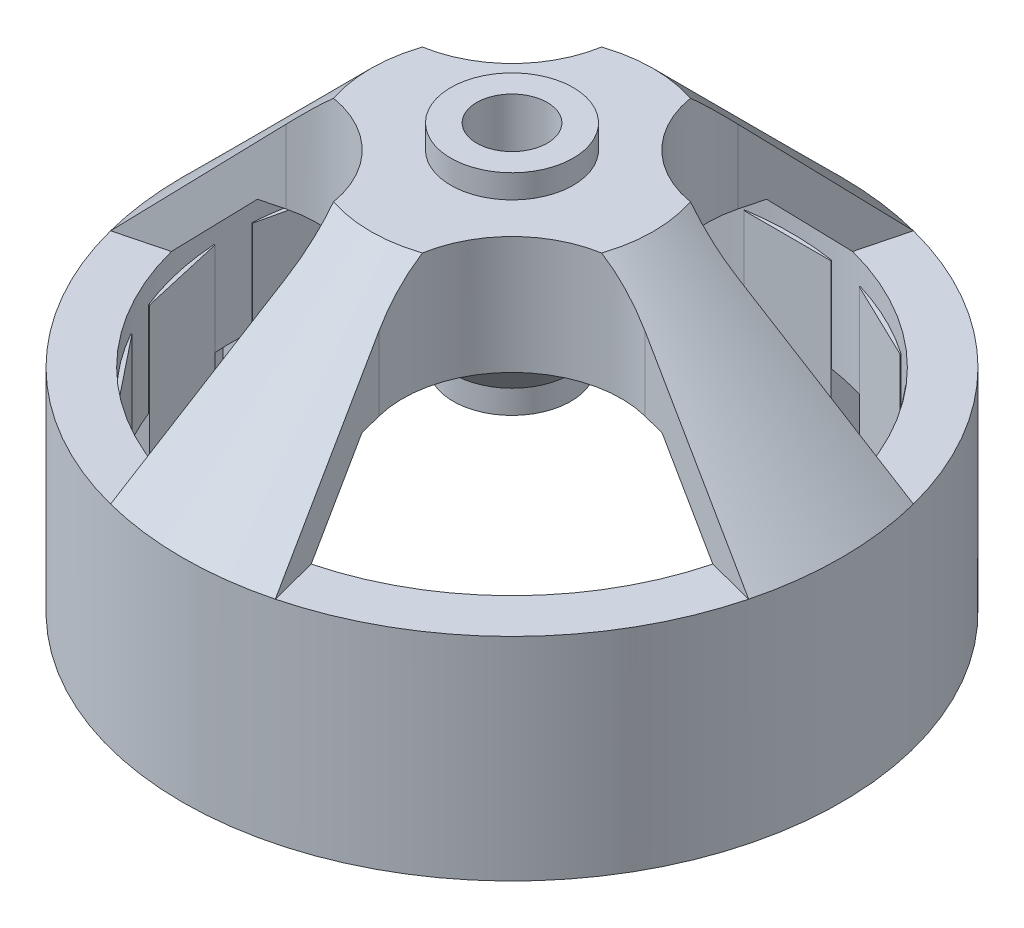
SolidWorks part; units mm, degrees
ref_plane "Front Plane" through (0, 0, 0) normal (0, 0, 1) x (1, 0, 0)
ref_plane "Top Plane" through (0, 0, 0) normal (0, 1, 0) x (1, 0, 0)
ref_plane "Right Plane" through (0, 0, 0) normal (1, 0, 0) x (0, 0, -1)
sketch "Sketch1" plane through (0, 0, 0) normal (0, 0, 1) x (1, 0, 0)
  line L0 (0, 0) -> (0, 18) construction
  line L1 (14, 0) -> (14, 9)
  line L2 (14, 9) -> (6, 17)
  line L3 (6, 17) -> (2.6, 17)
  line L4 (2.6, 17) -> (2.6, 18)
  line L5 (2.6, 18) -> (1.5, 18)
  line L6 (1.5, 18) -> (1.5, 9)
  line L7 (14, 0) -> (13.5, 0)
  line L8 (1.5, 9) -> (2.5, 9)
  line L9 (2.5, 9) -> (2.5, 10)
  line L10 (2.5, 10) -> (4.5, 12)
  line L11 (4.5, 12) -> (8.8787, 12)
  line L12 (8.8787, 12) -> (13.5, 7.3787)
  line L13 (13.5, 7.3787) -> (13.5, 0)
  dimension "D1" = 18
  dimension "D2" = 1
  dimension "D3" = 0.5
  dimension "D4" = 5.2
  dimension "D5" = 3
  dimension "D6" = 12
  dimension "D7" = 9
  dimension "D8" = 9
  dimension "D9" = 1.5
  dimension "D10" = 5
  dimension "D11" = 28
  dimension "D12" = 1
revolve "Revolve1" add sketch "Sketch1" angle 360 about L0
sketch "Sketch2" plane through (0, 17, 0) normal (0, 1, 0) x (1, 0, 0)
  line L0 (0, 0) -> (0, 14) construction
  line L1 (0, 0) -> (14, 0) construction
  line L2 (3.5, 13.5554) -> (1.9692, 7.6268)
  line L3 (13.5554, 3.5) -> (7.6268, 1.9692)
  line L4 (0, 0) -> (6.4658, 6.4658) construction
  line L5 (13.5554, -3.5) -> (7.6268, -1.9692)
  line L6 (3.5, -13.5554) -> (1.9692, -7.6268)
  line L7 (-3.5, -13.5554) -> (-1.9692, -7.6268)
  line L8 (-13.5554, -3.5) -> (-7.6268, -1.9692)
  line L9 (-13.5554, 3.5) -> (-7.6268, 1.9692)
  line L10 (-3.5, 13.5554) -> (-1.9692, 7.6268)
  circle A0 centre (0, 0) radius 14 construction
  arc A1 (1.9692, 7.6268) -> (7.6268, 1.9692) centre (6.4658, 6.4658) ccw
  circle A2 centre (0, 0) radius 4.5 construction
  arc A3 (3.5, 13.5554) -> (13.5554, 3.5) centre (0, 0) cw
  arc A4 (13.5554, -3.5) -> (3.5, -13.5554) centre (0, 0) cw
  arc A5 (7.6268, -1.9692) -> (1.9692, -7.6268) centre (6.4658, -6.4658) ccw
  arc A6 (-3.5, -13.5554) -> (-13.5554, -3.5) centre (0, 0) cw
  arc A7 (-1.9692, -7.6268) -> (-7.6268, -1.9692) centre (-6.4658, -6.4658) ccw
  arc A8 (-13.5554, 3.5) -> (-3.5, 13.5554) centre (0, 0) cw
  arc A9 (-7.6268, 1.9692) -> (-1.9692, 7.6268) centre (-6.4658, 6.4658) ccw
  point P11 (3.182, 3.182)
  point P32 (0, 0)
  dimension "D1" = 45
  dimension "D2" = 7
  dimension "D3" = 4
extrude "Cut-Extrude1" cut sketch "Sketch2" against normal up to surface (8 mm away) up to face at (0, 9, -2.5)
sketch "Sketch5" plane through (0, 9, 0) normal (0, 1, 0) x (1, 0, 0)
  circle A0 centre (0, 0) radius 14
  circle A1 centre (0, 0) radius 11.8787
  arc A2 (-13.5554, -3.5) -> (-3.5, -13.5554) centre (0, 0) ccw construction
  arc A3 (-11.5015, -2.9697) -> (-2.9697, -11.5015) centre (0, 0) ccw construction
extrude "Boss-Extrude2" add sketch "Sketch5" against normal offset from surface (5 mm away) 4 up to face at (0, 0, -14)
sketch "Sketch3" plane through (0, 0, 0) normal (0, -1, 0) x (1, 0, 0)
  line L0 (0, 0) -> (0, 13.5) construction
  line L1 (-1.85, 11.7) -> (1.85, 11.7)
  line L2 (-1.85, 11.7) -> (-1.85, 13.5)
  line L3 (-1.85, 13.5) -> (1.85, 13.5)
  line L4 (1.85, 11.7) -> (1.85, 13.5)
  line L5 (3.4096, 11.344) -> (6.7432, 9.7387)
  line L6 (3.4096, 11.344) -> (4.1906, 12.9658)
  line L7 (4.1906, 12.9658) -> (7.5242, 11.3604)
  line L8 (6.7432, 9.7387) -> (7.5242, 11.3604)
  line L9 (7.994, 8.7412) -> (10.3009, 5.8484)
  line L10 (7.994, 8.7412) -> (9.4013, 9.8635)
  line L11 (9.4013, 9.8635) -> (11.7082, 6.9707)
  line L12 (10.3009, 5.8484) -> (11.7082, 6.9707)
  line L13 (10.995, 4.4071) -> (11.8183, 0.7999)
  line L14 (10.995, 4.4071) -> (12.7499, 4.8076)
  line L15 (12.7499, 4.8076) -> (13.5732, 1.2004)
  line L16 (11.8183, 0.7999) -> (13.5732, 1.2004)
  line L17 (11.8183, -0.7999) -> (10.995, -4.4071)
  line L18 (11.8183, -0.7999) -> (13.5732, -1.2004)
  line L19 (13.5732, -1.2004) -> (12.7499, -4.8076)
  line L20 (10.995, -4.4071) -> (12.7499, -4.8076)
  line L21 (10.3009, -5.8484) -> (7.994, -8.7412)
  line L22 (10.3009, -5.8484) -> (11.7082, -6.9707)
  line L23 (11.7082, -6.9707) -> (9.4013, -9.8635)
  line L24 (7.994, -8.7412) -> (9.4013, -9.8635)
  line L25 (6.7432, -9.7387) -> (3.4096, -11.344)
  line L26 (6.7432, -9.7387) -> (7.5242, -11.3604)
  line L27 (7.5242, -11.3604) -> (4.1906, -12.9658)
  line L28 (3.4096, -11.344) -> (4.1906, -12.9658)
  line L29 (1.85, -11.7) -> (-1.85, -11.7)
  line L30 (1.85, -11.7) -> (1.85, -13.5)
  line L31 (1.85, -13.5) -> (-1.85, -13.5)
  line L32 (-1.85, -11.7) -> (-1.85, -13.5)
  line L33 (-3.4096, -11.344) -> (-6.7432, -9.7387)
  line L34 (-3.4096, -11.344) -> (-4.1906, -12.9658)
  line L35 (-4.1906, -12.9658) -> (-7.5242, -11.3604)
  line L36 (-6.7432, -9.7387) -> (-7.5242, -11.3604)
  line L37 (-7.994, -8.7412) -> (-10.3009, -5.8484)
  line L38 (-7.994, -8.7412) -> (-9.4013, -9.8635)
  line L39 (-9.4013, -9.8635) -> (-11.7082, -6.9707)
  line L40 (-10.3009, -5.8484) -> (-11.7082, -6.9707)
  line L41 (-10.995, -4.4071) -> (-11.8183, -0.7999)
  line L42 (-10.995, -4.4071) -> (-12.7499, -4.8076)
  line L43 (-12.7499, -4.8076) -> (-13.5732, -1.2004)
  line L44 (-11.8183, -0.7999) -> (-13.5732, -1.2004)
  line L45 (-11.8183, 0.7999) -> (-10.995, 4.4071)
  line L46 (-11.8183, 0.7999) -> (-13.5732, 1.2004)
  line L47 (-13.5732, 1.2004) -> (-12.7499, 4.8076)
  line L48 (-10.995, 4.4071) -> (-12.7499, 4.8076)
  line L49 (-10.3009, 5.8484) -> (-7.994, 8.7412)
  line L50 (-10.3009, 5.8484) -> (-11.7082, 6.9707)
  line L51 (-11.7082, 6.9707) -> (-9.4013, 9.8635)
  line L52 (-7.994, 8.7412) -> (-9.4013, 9.8635)
  line L53 (-6.7432, 9.7387) -> (-3.4096, 11.344)
  line L54 (-6.7432, 9.7387) -> (-7.5242, 11.3604)
  line L55 (-7.5242, 11.3604) -> (-4.1906, 12.9658)
  line L56 (-3.4096, 11.344) -> (-4.1906, 12.9658)
  circle A0 centre (0, 0) radius 13.5 construction
  point P64 (0, 0)
  dimension "D2" = 1.8
  dimension "D1" = 3.7
  dimension "D3" = 14
extrude "Boss-Extrude3" add sketch "Sketch3" against normal offset from surface (7 mm away) 1 from offset 1 up to face at (-8.5156, 9, -8.5156) offset against normal yes
